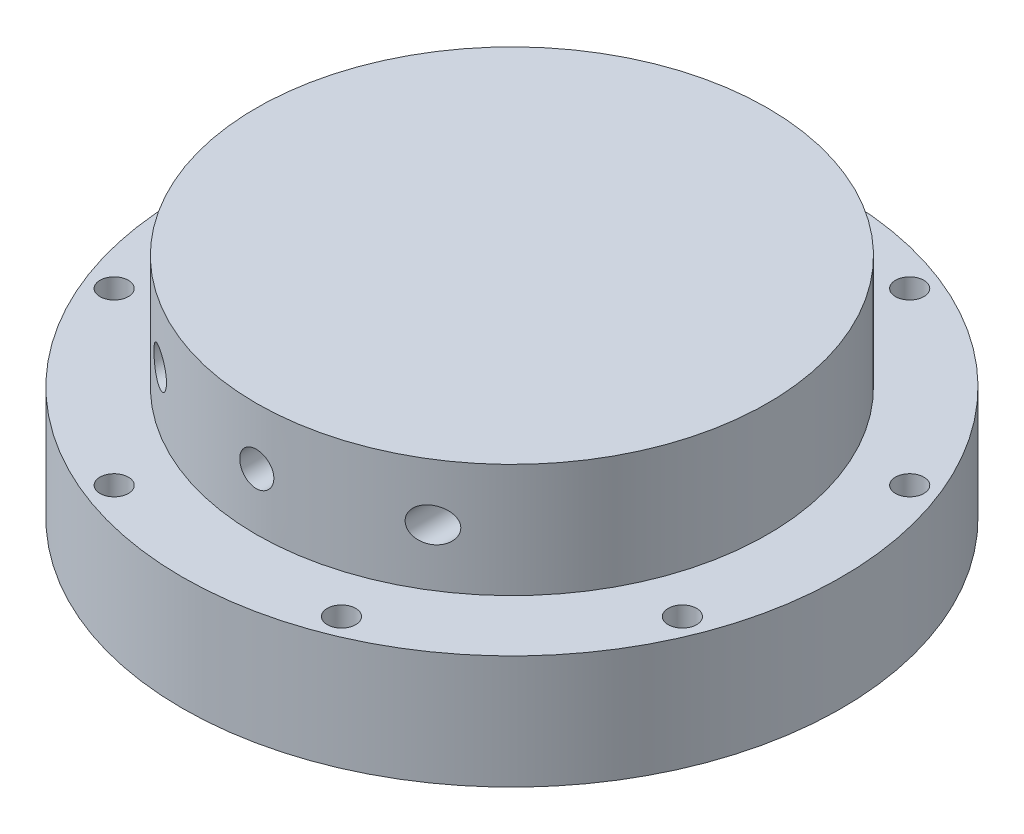
SolidWorks part; units mm, degrees
material "黄铜"
ref_plane "前视基准面" through (0, 0, 0) normal (0, 0, 1) x (1, 0, 0)
ref_plane "上视基准面" through (0, 0, 0) normal (0, 1, 0) x (1, 0, 0)
ref_plane "右视基准面" through (0, 0, 0) normal (1, 0, 0) x (0, 0, -1)
sketch "草图1" plane through (0, 0, 0) normal (0, 1, 0) x (1, 0, 0)
  line L0 (0, 0) -> (0, 29) construction
  circle A0 centre (0, 0) radius 29
  circle A1 centre (10, 25) radius 1.25
  circle A2 centre (-10, 25) radius 1.25
  circle A3 centre (25, -10) radius 1.25
  circle A4 centre (25, 10) radius 1.25
  circle A5 centre (-10, -25) radius 1.25
  circle A6 centre (10, -25) radius 1.25
  circle A7 centre (-25, 10) radius 1.25
  circle A8 centre (-25, -10) radius 1.25
  dimension "D1" = 58
  dimension "D2" = 2.5
  dimension "D3" = 10
  dimension "D4" = 25
  dimension "D5" = 4
extrude "隔热台底座" add sketch "草图1" against normal blind 10
sketch "草图2" plane through (0, 0, 0) normal (0, 1, 0) x (1, 0, 0)
  circle A0 centre (0, 0) radius 22.5
  dimension "D1" = 45
extrude "加热台底座" add sketch "草图2" along normal blind 10
ref_plane "加热棒基准面" through (0, 0, 22.5) normal (0, 0, 1) x (1, 0, 0)
sketch "草图3" plane through (0, 0, 22.5) normal (0, 0, 1) x (1, 0, 0)
  line L0 (0, 0.1797) -> (0, 16.7559) construction
  line L1 (22.5, 10) -> (-22.5, 10) construction
  circle A0 centre (0, 5) radius 1.5
  circle A1 centre (12, 5) radius 1.5
  circle A2 centre (-12, 5) radius 1.5
  point P8 (0, 0)
  dimension "D1" = 3
  dimension "D2" = 12
  dimension "D3" = 12
  dimension "D4" = 5
extrude "M3*3 加热棒通孔" cut sketch "草图3" against normal through all
sketch "草图4" plane through (0, -10, 0) normal (0, -1, 0) x (1, 0, 0)
  line L0 (0, 0) -> (29, 0) construction
  circle A1 centre (12, 0) radius 1.5
  dimension "D1" = 3
  dimension "D2" = 12
extrude "M3*3 加热棒固定孔" cut sketch "草图4" against normal up to surface (13.5 mm away) up to face at (10.5388, 5.3391, 19.8792)
thread "M3*3 加热棒固定螺纹线" pitch 0.5 method cut profile "螺纹线轮廓1" start angle 0, offset 0, length 13, pitch 0.5, diameter 3
ref_plane "基准面2" through (13.5, -10, 0) normal (0, 0, 1) x (1, 0, 0)
sketch "螺纹线轮廓1" plane through (13.5, -10, 0) normal (0, 0, 1) x (1, 0, 0)
  line L0 (0, 0) -> (0, 0.5) construction
  line L1 (0, 0) -> (0.2706, 0.1562)
  line L2 (0.2706, 0.1562) -> (0.2706, 0.2187)
  line L3 (0.2706, 0.2187) -> (0, 0.375)
  line L4 (0.2706, 0.1875) -> (0, 0.1875) construction
  line L11 (0, 0) -> (0, 0.375)
  point P2 (0, 0)
  dimension "Pitch" = 0.5
  dimension "Profile_Angle" = 60
  dimension "Profile_Land" = 0.0625
  dimension "Profile_Height" = 0.2706
pattern_linear "M3*3 加热棒固定孔阵列" count 3 spacing 12 along (-1, 0, 0) of "M3*3 加热棒固定螺纹线", "M3*3 加热棒固定孔"
sketch "草图7" plane through (0, -10, 0) normal (0, -1, 0) x (1, 0, 0)
  circle A0 centre (0, 0) radius 25
  dimension "D1" = 50
extrude "扇热底部" cut sketch "草图7" against normal blind 7
